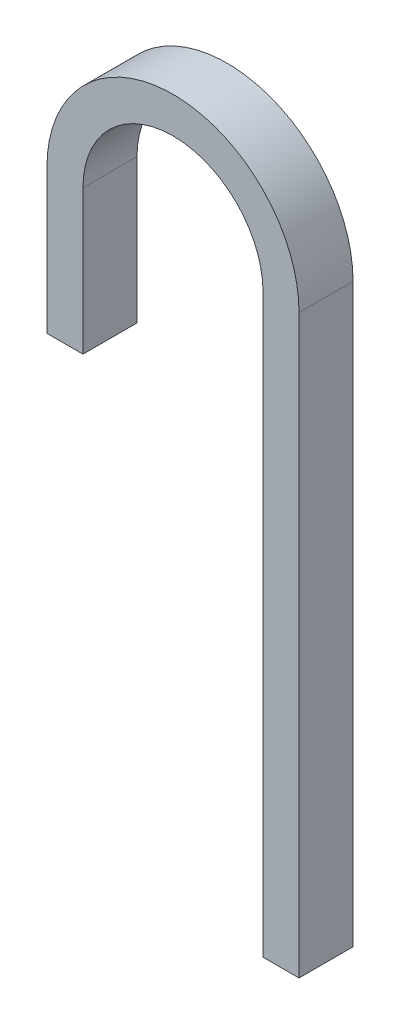
SolidWorks part; units mm, degrees
ref_plane "Front Plane" through (0, 0, 0) normal (0, 0, 1) x (1, 0, 0)
ref_plane "Top Plane" through (0, 0, 0) normal (0, 1, 0) x (1, 0, 0)
ref_plane "Right Plane" through (0, 0, 0) normal (1, 0, 0) x (0, 0, -1)
sketch "Sketch5" plane through (0, 0, 0) normal (0, 0, 1) x (1, 0, 0)
  line L0 (0, 0) -> (12.7, 0)
  line L1 (12.7, 0) -> (12.7, 203.2)
  line L2 (0, 0) -> (0, 203.2)
  line L4 (-76.2, 203.2) -> (-76.2, 152.4)
  line L5 (-76.2, 152.4) -> (-63.5, 152.4)
  line L6 (-63.5, 152.4) -> (-63.5, 203.2)
  arc A0 (0, 203.2) -> (-63.5, 203.2) centre (-31.75, 203.2) ccw
  arc A1 (12.7, 203.2) -> (-76.2, 203.2) centre (-31.75, 203.2) ccw
  point P9 (0, 0)
  point P12 (-31.75, 149.5682)
  dimension "D1" = 31.75
  dimension "D2" = 44.45
  dimension "D3" = 50.8
  dimension "D4" = 203.2
extrude "Boss-Extrude1" add sketch "Sketch5" along normal blind 19.05 contours A0 L6 L5 L4 A1 L1 L0 L2
